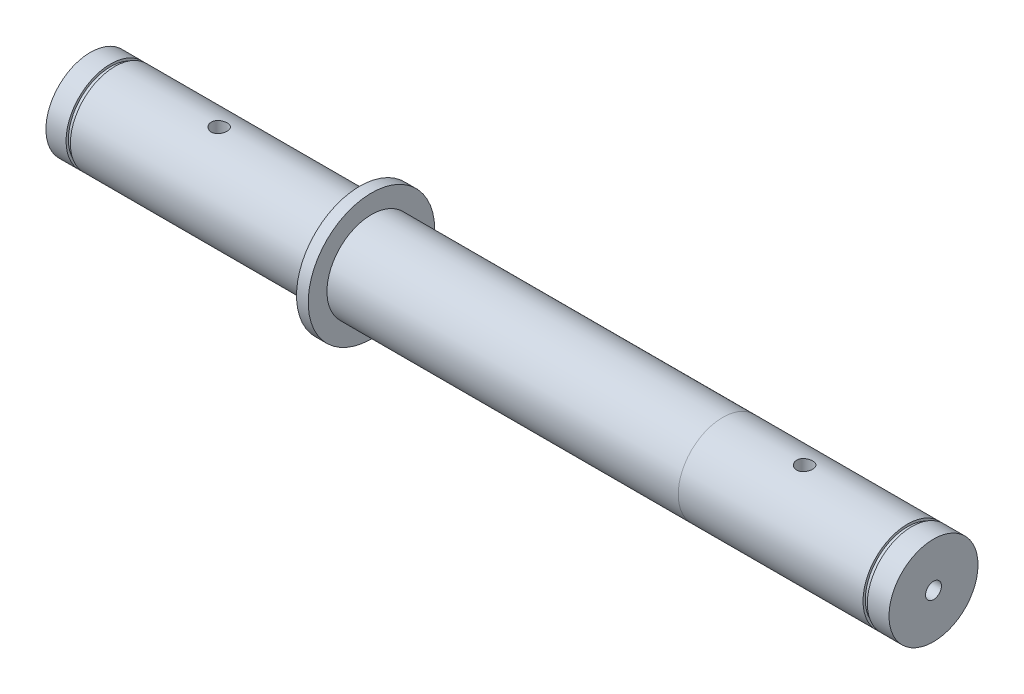
SolidWorks part; units mm, degrees
material "1.7225 (42CrMo4)"
ref_plane "E_Oben" through (0, 0, 0) normal (0, 0, 1) x (1, 0, 0)
ref_plane "E_Vorne" through (0, 0, 0) normal (0, 1, 0) x (1, 0, 0)
ref_plane "E_Rechts" through (0, 0, 0) normal (1, 0, 0) x (0, 0, -1)
ref_axis "A_Drehachse" through (-88.99, 0, 0) along (1, 0, 0)
sketch "Skizze1" plane through (0, 0, 0) normal (0, 0, 1) x (1, 0, 0)
  line L1 (0, -55) -> (0, 55) construction
  line L3 (180, 19) -> (180, 0)
  line L4 (180, 0) -> (-180, 0)
  line L7 (-180, 19) -> (-180, 0)
  line L10 (-65, 19) -> (-65, 27)
  line L11 (-65, 27) -> (-60, 27)
  line L12 (-60, 27) -> (-60, 19.0001)
  line L13 (-180, 19) -> (-65, 19)
  line L14 (-60, 19.0001) -> (90, 19.0001)
  line L15 (90, 19.0001) -> (90, 19)
  line L16 (90, 19) -> (180, 19)
  point P12 (0, 0)
  point P19 (-62.5, 27)
  dimension "D1" = 19.0001
  dimension "D2" = 19
  dimension "D3" = 19
  dimension "D4" = 360
  dimension "D5" = 115
  dimension "D6" = 5
  dimension "D7" = 27
  dimension "D8" = 150
revolve "Rotation1" add sketch "Skizze1" angle 360 about L4
hole_wizard "M8 Tapped Hole1" positions "Skizze13" profile "Skizze14" tap size "M8" standard "DIN"
sketch "Skizze13" plane through (180, 0, 0) normal (1, 0, 0) x (0, 0, -1)
  point P0 (0, 0)
  point P3 (0, 0)
sketch "Skizze14" plane through (180, 0, 0) normal (0, 1, 0) x (0, 0, -1)
  line L0 (0, 0) -> (0, 67.0429)
  line L1 (0, 67.0429) -> (3.4, 65)
  line L2 (3.4, 65) -> (3.4, 0)
  line L5 (3.4, 0) -> (0, 0)
  line L10 (0, 67.0429) -> (-3.4, 65) construction
  line L11 (0, -6.35) -> (0, 107.95) construction
  dimension "Bohrerdurchmesser" = 6.8
  dimension "Bohrungstiefe" = 65
  dimension "Spitzenwinkel" = 118
cosmetic thread "Bohrungsgewinde2" parameters "D1"=20, "D2"=8
hole_wizard "M8 Gewindebohrung3" positions "Skizze17" profile "Skizze18" tap size "M8" standard "DIN" end condition through all
sketch "Skizze17" plane through (0, 0, 0) normal (0, 1, 0) x (1, 0, 0)
  line L0 (-29.7, 0) -> (29.7, 0) construction
  line L1 (-88.99, 0) -> (88.99, 0) construction
  line L3 (180, -19) -> (180, 19) construction
  point P0 (-125, 0)
  point P4 (125, 0)
  dimension "D3" = 305
  dimension "D4" = 55
sketch "Skizze18" plane through (-125, 0, 0) normal (1, 0, 0) x (0, 0, -1)
  line L0 (0, 0) -> (0, 27)
  line L1 (0, 27) -> (3.4, 27)
  line L2 (3.4, 27) -> (3.4, 0)
  line L5 (3.4, 0) -> (0, 0)
  line L11 (0, -6.35) -> (0, 107.95) construction
  dimension "Bohrerdurchmesser" = 6.8
  dimension "Bohrungstiefe" = 27
mirror "Spiegeln2" about plane through (0, 0, 0) normal (0, 1, 0) of "M8 Gewindebohrung3"
sketch "Skizze19" plane through (0, 0, 0) normal (0, 0, 1) x (1, 0, 0)
  line L8 (180, 19) -> (128.4, 19) construction
  line L9 (168.9, 19) -> (170.75, 19)
  line L10 (168.9, 19) -> (168.9, 18)
  line L11 (168.9, 18) -> (170.75, 18)
  line L12 (170.75, 19) -> (170.75, 18)
  line L13 (180, -19) -> (180, 19) construction
  dimension "D1" = 9.25
  dimension "D2" = 1
  dimension "D4" = 1.85
revolve "Schnitt-Rotation1" cut sketch "Skizze19" angle 360 about axis through (-88.99, 0, 0) along (1, 0, 0)
sketch "Skizze20" plane through (0, 0, 0) normal (0, 0, 1) x (1, 0, 0)
  line L9 (-128.3999, 19) -> (-180, 19) construction
  line L10 (-180, 19) -> (-180, -19) construction
  line L11 (-171.4, 19) -> (-169.55, 19)
  line L12 (-171.4, 19) -> (-171.4, 18)
  line L13 (-171.4, 18) -> (-169.55, 18)
  line L14 (-169.55, 19) -> (-169.55, 18)
  dimension "D1" = 8.6
  dimension "D4" = 1
  dimension "D5" = 1.85
revolve "Schnitt-Rotation2" cut sketch "Skizze20" angle 360 about axis through (-88.99, 0, 0) along (1, 0, 0)
sketch "Sketch3" plane through (-180, 0, 0) normal (-1, 0, 0) x (0, 0, 1)
  point P0 (0, 0)
hole_wizard "M8 Tapped Hole2" positions "Sketch3" profile "Sketch2" tap size "M8" standard "DIN"
sketch "Sketch2" plane through (-180, 0, 0) normal (0, 1, 0) x (0, 0, 1)
  line L0 (0, 0) -> (0, 67.0429)
  line L1 (0, 67.0429) -> (3.4, 65)
  line L2 (3.4, 65) -> (3.4, 0)
  line L5 (3.4, 0) -> (0, 0)
  line L10 (0, 67.0429) -> (-3.4, 65) construction
  line L11 (0, -6.35) -> (0, 107.95) construction
  dimension "Tap Drill Dia." = 6.8
  dimension "Tap Drill Depth" = 65
  dimension "Drill Angle" = 118
cosmetic thread "Hole Thread1" parameters "D1"=20, "D2"=8
